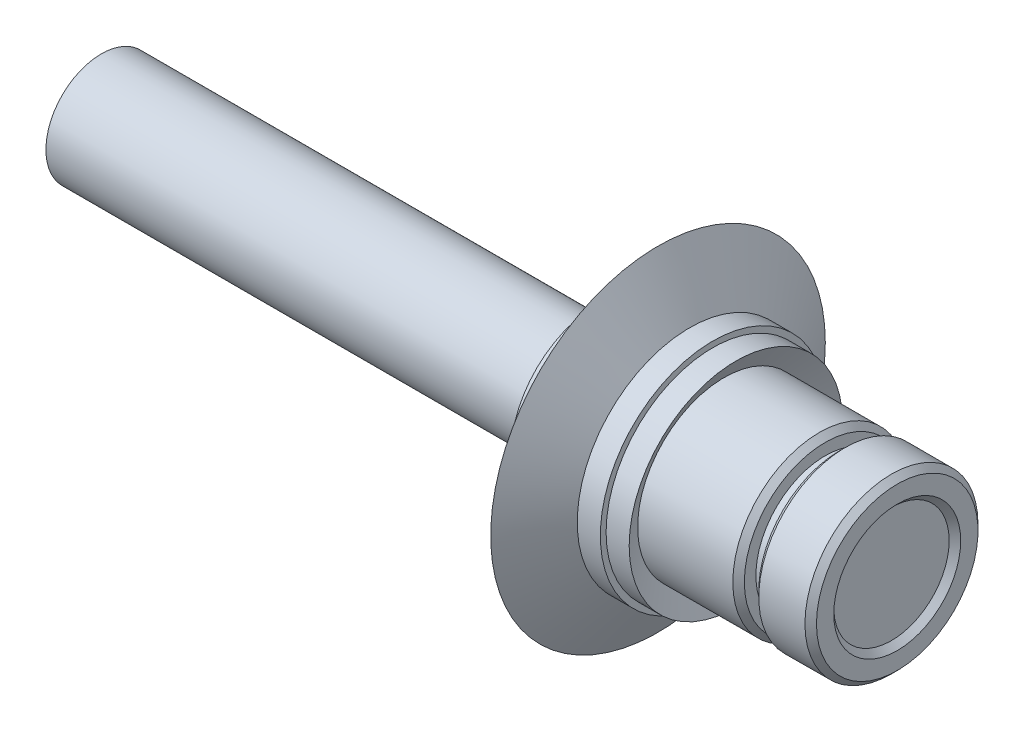
SolidWorks part; units mm, degrees
material "3.1305 (EN-AW 2117)"
ref_plane "Plan de face" through (0, 0, 0) normal (0, 0, 1) x (1, 0, 0)
ref_plane "Plan de dessus" through (0, 0, 0) normal (0, 1, 0) x (1, 0, 0)
ref_plane "Plan de droite" through (0, 0, 0) normal (1, 0, 0) x (0, 0, -1)
sketch "Esquisse1" plane through (0, 0, 0) normal (0, 0, 1) x (1, 0, 0)
  line L0 (438.9646, -15) -> (438.9646, -12)
  line L1 (438.9646, -12) -> (441.4646, -12)
  line L2 (441.4646, -12) -> (441.4646, -15)
  line L3 (410, -15) -> (399.5, -15)
  line L4 (399.5, -15) -> (399.5, -9.6)
  line L5 (410, -29) -> (410, -15)
  line L6 (451.4646, -10) -> (450.4646, -10)
  line L7 (450.4646, -10) -> (450.4646, 0)
  line L8 (415.5, -19.5) -> (410, -29)
  line L9 (421.4646, -15) -> (421.4646, 0) construction
  line L10 (438.9646, -15) -> (421.4646, -15)
  line L11 (419.5, -19.5) -> (415.5, -19.5)
  line L12 (313.5, -7.6) -> (316.5, -7.6)
  line L13 (316.5, -7.6) -> (316.5, 0)
  line L14 (313.5, 0) -> (316.5, 0) construction
  line L15 (423.5, -18.5) -> (419.5, -18.5)
  line L18 (451.4646, -10) -> (451.4646, -15)
  line L19 (451.4646, -15) -> (441.4646, -15)
  line L21 (313.5, -9.6) -> (313.5, -7.6)
  line L22 (399.5, -9.6) -> (313.5, -9.6)
  line L24 (316.5, 0) -> (450.4646, 0) construction
  line L25 (313.5, 0) -> (276.6306, 0) construction
  line L27 (316.5, 0) -> (450.4646, 0)
  line L30 (419.5, -18.5) -> (419.5, -19.5)
  line L31 (421.4646, -15) -> (423.5, -18.5)
  dimension "D1" = 86
  dimension "D2" = 9.6
  dimension "D3" = 10.5
  dimension "D4" = 5.5
  dimension "D5" = 4
  dimension "D6" = 4
  dimension "D7" = 30
  dimension "D8" = 5
  dimension "D9" = 10
  dimension "D10" = 1
  dimension "D11" = 10
  dimension "D12" = 2.5
  dimension "D13" = 3
  dimension "D14" = 15
  dimension "D15" = 2
  dimension "D16" = 3
revolve "Révolution2" add sketch "Esquisse1" angle 360 about L25
chamfer "Chanfrein1" distance 1 angle 45 4 edges at (438.9646, 0, -15) (441.4646, 0, -15) (451.4646, 0, -15) (451.4646, 0, -10)
